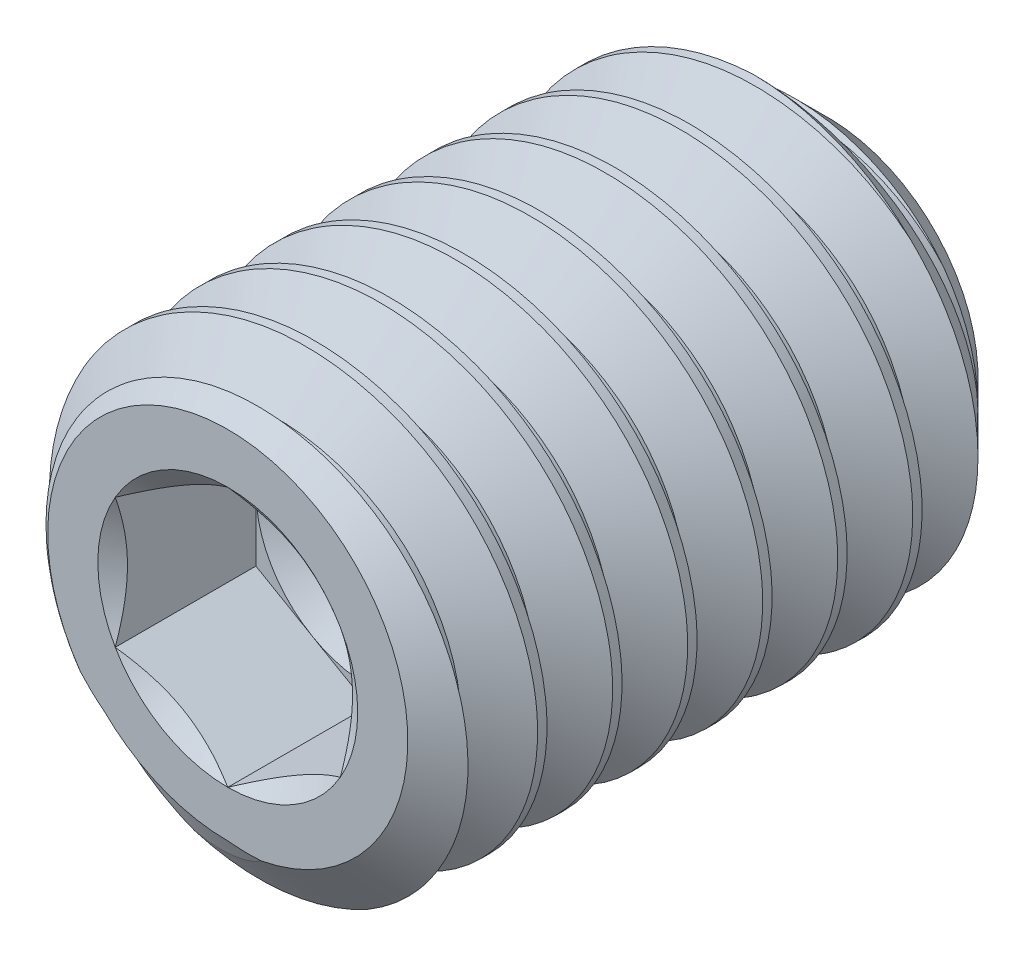
SolidWorks part; units mm, degrees
ref_plane "Front" through (0, 0, 0) normal (0, 0, 1) x (1, 0, 0)
ref_plane "Top" through (0, 0, 0) normal (0, 1, 0) x (1, 0, 0)
ref_plane "Right" through (0, 0, 0) normal (1, 0, 0) x (0, 0, -1)
sketch "Body Sketch" plane through (0, 0, 0) normal (1, 0, 0) x (0, 0, -1)
  line L0 (-2, 0) -> (-2, 1.2)
  line L1 (-2, 1.2) -> (-1.7899, 1.5)
  line L2 (-1.7899, 1.5) -> (1.5, 1.5)
  line L3 (1.5, 1.5) -> (2, 1)
  line L4 (-0.145, 1.5) -> (-0.145, -1.5) construction
  line L5 (2, 0) -> (-2, 0)
  line L6 (-2, 1.2) -> (-2, -1.2) construction
  line L7 (2, 0) -> (2, 1)
  point P11 (-0.145, 0)
  dimension "Length" = 4
  dimension "Top Chamfer" = 35
  dimension "D6" = 45
  dimension "Diameter" = 3
  dimension "D1" = 2.4
  dimension "Tip Chamfer" = 0.5
revolve "Body Revolve" add sketch "Body Sketch" angle 360 about L5
ref_plane "Bottom of Tip Plane" through (0, 0, -2) normal (0, 0, 1) x (1, 0, 0)
sketch "Spiral Sketch" plane through (0, 0, -2) normal (0, 0, 1) x (1, 0, 0)
  circle A0 centre (0, 0) radius 1.5 construction
  circle A1 centre (0, 0) radius 1.5
curve "Helix/Spiral" pitch 0.5 height 4.5 radius 1.5 centre (0, 0, -2) axis (0, 0, 1) start towards (0, 1, 0) parameters "Thread Pitch"=0.5
sketch "Cut Sweep Sketch" plane through (0, 0, 0) normal (1, 0, 0) x (0, 0, -1)
  line L0 (2, 1.5) -> (2.4375, 1.5)
  line L1 (2.4375, 1.5) -> (2.25, 1.1752)
  line L2 (2.25, 1.1752) -> (2.1875, 1.1752)
  line L3 (2.1875, 1.1752) -> (2, 1.5)
  line L4 (2.0938, 1.3376) -> (2.3438, 1.3376) construction
  line L6 (-1.7899, 1.5) -> (1.5, 1.5) construction
  dimension "D1" = 0.0625
  dimension "D3" = 60
  dimension "D2" = 0.25
sweep "Cut Sweep" cut profiles "Cut Sweep Sketch" path "Helix/Spiral" align with end faces yes
sketch "Hex Sketch" plane through (0, 0, 2) normal (0, 0, 1) x (1, 0, 0)
  line L1 (0, 0.866) -> (-0.75, 0.433)
  line L2 (-0.75, 0.433) -> (-0.75, -0.433)
  line L3 (-0.75, -0.433) -> (0, -0.866)
  line L4 (0, -0.866) -> (0.75, -0.433)
  line L5 (0.75, -0.433) -> (0.75, 0.433)
  line L6 (0.75, 0.433) -> (0, 0.866)
  circle A0 centre (0, 0) radius 0.75 construction
  dimension "Hex" = 1.5
extrude "Hex Extrude" cut sketch "Hex Sketch" against normal blind 0.9375
sketch "Hex Entry Sketch" plane through (0, 0, 2) normal (0, 0, 1) x (1, 0, 0)
  circle A0 centre (0, 0) radius 0.866
extrude "Hex Entry Extrude" cut sketch "Hex Entry Sketch" against normal through all draft 55
sketch "Hex Bottom Sketch" plane through (0, 0, 1.0625) normal (0, 0, 1) x (1, 0, 0)
  circle A0 centre (0, 0) radius 0.75 construction
  circle A1 centre (0, 0) radius 0.75
extrude "Hex Bottom Extrude" cut sketch "Hex Bottom Sketch" against normal through all draft 60
equation "\"D1@Cut Sweep Sketch\" = \"Thread Pitch@Helix/Spiral\" * .125"
equation "\"D2@Cut Sweep Sketch\" = \"Thread Pitch@Helix/Spiral\" * .5"
equation "\"D3@Helix/Spiral\" = \"Length@Body Sketch\" + \"Thread Pitch@Helix/Spiral\""
equation "\"hex Depth@Hex Extrude\" = \"Hex@Hex Sketch\" * .625"
equation "\"D1@Body Sketch\" = \"Diameter@Body Sketch\" * .8"
equation "\"Tip Chamfer@Body Sketch\" = \"Thread Pitch@Helix/Spiral\""
equation "\"Diameter\"= 3mm"
equation "\"Thread Pitch\"= 0.5mm"
equation "\"Hex Size\"= 1.5mm"
equation "\"Diameter@Body Sketch\"=\"Diameter\""
equation "\"Thread Pitch@Helix/Spiral\"     = \"Thread Pitch\""
equation "\"Hex@Hex Sketch\" = \"Hex Size\""
